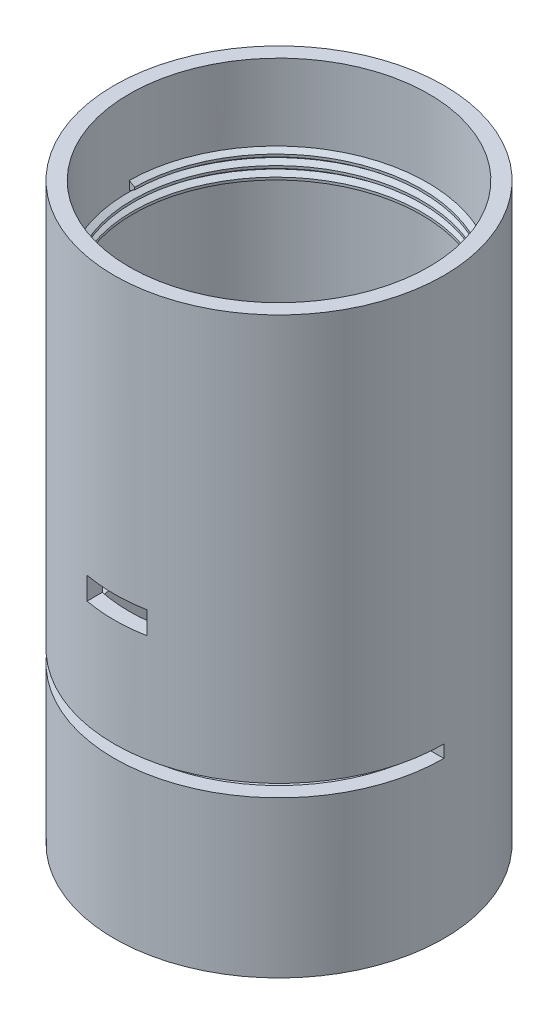
SolidWorks part; units mm, degrees
material "ABS"
ref_plane "Front Plane" through (0, 0, 0) normal (0, 0, 1) x (1, 0, 0)
ref_plane "Top Plane" through (0, 0, 0) normal (0, 1, 0) x (1, 0, 0)
ref_plane "Right Plane" through (0, 0, 0) normal (1, 0, 0) x (0, 0, -1)
sketch "Sketch1" plane through (0, 0, 0) normal (0, 1, 0) x (1, 0, 0)
  circle A0 centre (0, 0) radius 33
  dimension "D1" = 66
extrude "Boss-Extrude1" add sketch "Sketch1" along normal blind 99
shell "Shell1" thickness 3
sketch "Sketch2" plane through (0, 99, 0) normal (0, 1, 0) x (1, 0, 0)
  circle A0 centre (0, 0) radius 30
extrude "Cut-Extrude1" cut sketch "Sketch2" against normal blind 3
sketch "Sketch3" plane through (0, 0, 0) normal (0, -1, 0) x (1, 0, 0)
  circle A0 centre (0, 0) radius 33
extrude "Boss-Extrude2" add sketch "Sketch3" along normal blind 16
sketch "Sketch4" plane through (0, -16, 0) normal (0, -1, 0) x (1, 0, 0)
  line L1 (24.25, 13.25) -> (-24.25, 13.25)
  line L2 (24.25, 13.25) -> (24.25, -13.25)
  line L3 (24.25, -13.25) -> (-24.25, -13.25)
  line L4 (-24.25, 13.25) -> (-24.25, -13.25)
  line L5 (24.25, 13.25) -> (-24.25, -13.25) construction
  line L6 (24.25, -13.25) -> (-24.25, 13.25) construction
  point P0 (0, 0)
  dimension "D1" = 26.5
  dimension "D2" = 48.5
extrude "Cut-Extrude2" cut sketch "Sketch4" against normal blind 18
sketch "Sketch5" plane through (0, 0, 0) normal (0, 0, 1) x (1, 0, 0)
  line L0 (33, 41.5) -> (-33, 41.5) construction
  line L1 (33, -16) -> (33, 99) construction
  line L2 (-33, 99) -> (-33, -16) construction
  line L3 (-21.4863, 41.5) -> (-21.4863, 16.5) construction
  line L4 (6, 43.75) -> (-6, 43.75)
  line L5 (6, 43.75) -> (6, 39.25)
  line L6 (6, 39.25) -> (-6, 39.25)
  line L7 (-6, 43.75) -> (-6, 39.25)
  line L8 (6, 43.75) -> (-6, 39.25) construction
  line L9 (6, 39.25) -> (-6, 43.75) construction
  line L10 (-21.4863, 16.5) -> (33, 16.5) construction
  line L15 (33, 16.5) -> (-33, 16.5) construction
  line L17 (33, 17.75) -> (-33, 17.75)
  line L18 (33, 17.75) -> (33, 15.25)
  line L19 (33, 15.25) -> (-33, 15.25)
  line L20 (-33, 17.75) -> (-33, 15.25)
  line L21 (33, 17.75) -> (-33, 15.25) construction
  line L22 (33, 15.25) -> (-33, 17.75) construction
  point P6 (0, 41.5)
  point P13 (0, 13)
  point P14 (0, 16.5)
  dimension "D1" = 4.5
  dimension "D2" = 12
  dimension "D3" = 25
  dimension "D4" = 2.5
extrude "Cut-Extrude3" cut sketch "Sketch5" along normal blind 50
sketch "Sketch7" plane through (0, -16, 0) normal (0, -1, 0) x (-1, 0, 0)
  text T0 "SST LAB" font "Rockwell Nova Cond" height in points 16
extrude "Cut-Extrude4" cut sketch "Sketch7" against normal blind 1
sketch "Sketch12" plane through (-24.25, 0, 0) normal (1, 0, 0) x (0, 0, -1)
  line L1 (11.7616, -15.413) -> (7.7616, -15.413)
  line L2 (11.7616, -15.413) -> (11.7616, -14.413)
  line L3 (11.7616, -14.413) -> (7.7616, -14.413)
  line L4 (7.7616, -15.413) -> (7.7616, -14.413)
  line L5 (11.7616, -15.413) -> (7.7616, -14.413) construction
  line L6 (11.7616, -14.413) -> (7.7616, -15.413) construction
  line L7 (-7.2384, -15.5273) -> (-11.2384, -15.5273)
  line L8 (-7.2384, -15.5273) -> (-7.2384, -14.5273)
  line L9 (-7.2384, -14.5273) -> (-11.2384, -14.5273)
  line L10 (-11.2384, -15.5273) -> (-11.2384, -14.5273)
  line L11 (-7.2384, -15.5273) -> (-11.2384, -14.5273) construction
  line L12 (-7.2384, -14.5273) -> (-11.2384, -15.5273) construction
  point P0 (9.7616, -14.913)
  point P5 (-9.2384, -15.0273)
  point P10 (-9.2384, -15.5273)
  dimension "D1" = 15
  dimension "D2" = 1
  dimension "D3" = 4
  dimension "D4" = 4
  dimension "D5" = 1
extrude "Cut-Extrude5" cut sketch "Sketch12" against normal blind 3
thread "Thread1" pitch 2 method extrude profile "Thread Profile1" start angle 0, offset 15, length 5, pitch 2, diameter 60
ref_plane "Plane1" through (-30, 84, 0) normal (0, 0, 1) x (-1, 0, 0)
sketch "Thread Profile1" plane through (-30, 84, 0) normal (0, 0, 1) x (-1, 0, 0)
  line L0 (0, 0) -> (0, 2) construction
  line L11 (0, 0) -> (0, 1.75)
  line L12 (0, 1.75) -> (-1.0825, 1.125)
  line L13 (-1.0825, 1.125) -> (-1.0825, 0.625)
  line L15 (-1.0825, 0.625) -> (0, 0)
  line L17 (-1.0825, 0.875) -> (0, 0.875) construction
  point P2 (0, 0)
  dimension "Pitch" = 2
  dimension "Profile_Angle" = 60
  dimension "Profile_Land" = 0.5
  dimension "Profile_Height" = 1.0825
